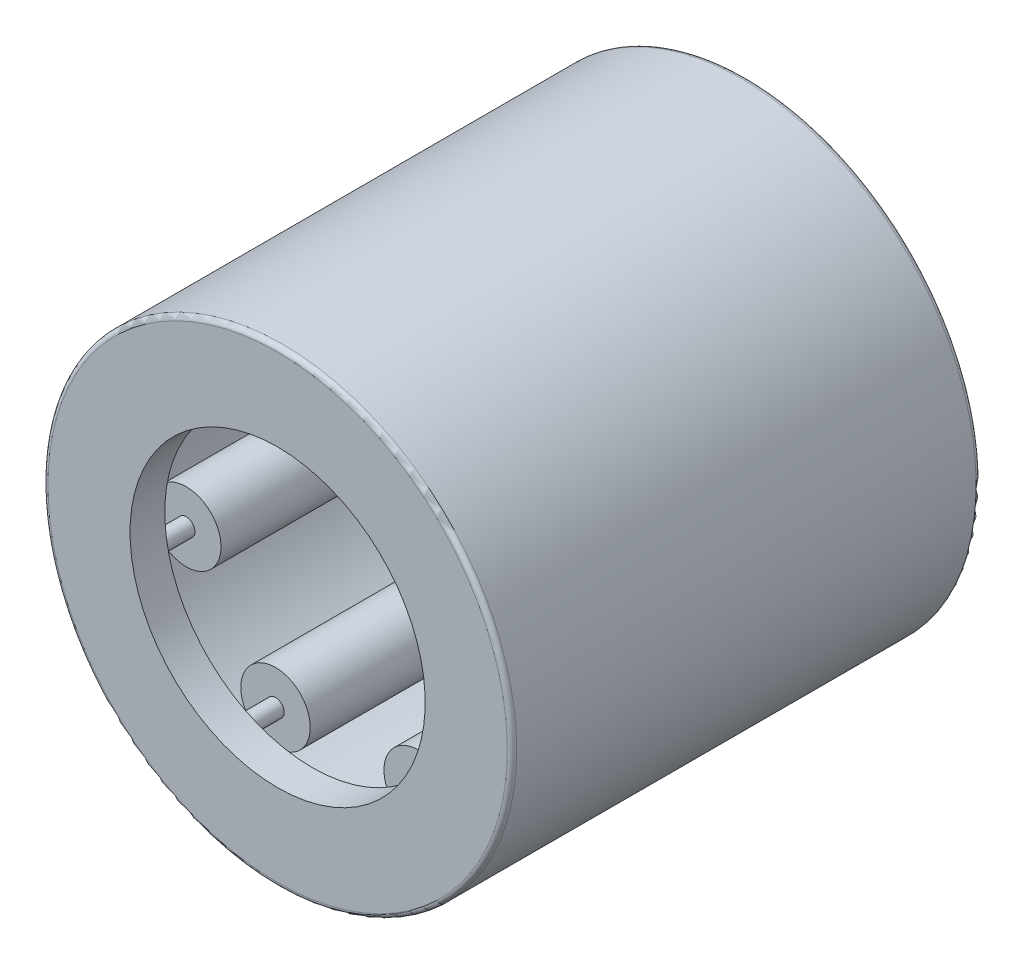
SolidWorks part; units mm, degrees
ref_plane "Front Plane" through (0, 0, 0) normal (0, 0, 1) x (1, 0, 0)
ref_plane "Top Plane" through (0, 0, 0) normal (0, 1, 0) x (1, 0, 0)
ref_plane "Right Plane" through (0, 0, 0) normal (1, 0, 0) x (0, 0, -1)
sketch "Sketch1" plane through (0, 0, 0) normal (1, 0, 0) x (0, 0, -1)
  line L0 (-4.5, 0) -> (4.5, 0) construction
  line L1 (0, 0) -> (0, 4.5) construction
  line L2 (-4.5, 0) -> (-4.5, 4.5) construction
  line L3 (-4.5, 4.5) -> (4.5, 4.5)
  line L4 (4.5, 4.5) -> (4.5, 0) construction
  line L5 (4.5, 0) -> (3.8333, 0) construction
  line L6 (3.8333, 0) -> (3.8333, 3.8333) construction
  line L7 (3.8333, 3.8333) -> (-3.8333, 3.8333)
  line L8 (-3.8333, 3.8333) -> (-3.8333, 0) construction
  line L9 (-3.8333, 0) -> (-4.5, 0) construction
  line L10 (-4.5, 4.5) -> (-4.5, 2.8333)
  line L11 (-4.5, 2.8333) -> (-3.8333, 2.8333)
  line L12 (-3.8333, 2.8333) -> (-3.8333, 3.8333)
  line L13 (3.8333, 4.5) -> (3.8333, 3.8333) construction
  line L14 (3.8333, 3.8333) -> (3.8333, 2.8333)
  line L15 (3.8333, 2.8333) -> (4.5, 2.8333)
  line L16 (4.5, 2.8333) -> (4.5, 4.5)
  line L17 (3.8333, 3.8333) -> (3.8333, 3.1667) construction
  line L18 (3.8333, 3.1667) -> (3.8333, 2.5) construction
  line L19 (3.8333, -3.8333) -> (3.8333, -3.1667) construction
  line L20 (3.8333, -4.5) -> (3.8333, -3.8333) construction
  line L21 (4.5, -2.8333) -> (4.5, -4.5) construction
  line L22 (3.8333, -2.8333) -> (4.5, -2.8333) construction
  line L23 (3.8333, -3.8333) -> (3.8333, -2.8333) construction
  line L24 (-3.8333, -2.8333) -> (-3.8333, -3.8333) construction
  line L25 (-4.5, -2.8333) -> (-3.8333, -2.8333) construction
  line L26 (-4.5, -4.5) -> (-4.5, -2.8333) construction
  line L27 (3.8333, -3.8333) -> (-3.8333, -3.8333) construction
  line L28 (-4.5, -4.5) -> (4.5, -4.5) construction
  point P4 (0, 2.5)
  dimension "C | Width" = 9
  dimension "Fw | ID" = 5
  dimension "D | OD" = 9
sketch "Sketch7" plane through (0, 0, 0) normal (1, 0, 0) x (0, 0, -1)
  line L0 (-4.5, 4.5) -> (-4.5, 2.8333) construction
  line L1 (-4.5, 2.8333) -> (-3.8333, 2.8333) construction
  line L2 (-3.8333, 2.8333) -> (-3.8333, 3.8333) construction
  line L3 (3.8333, 3.8333) -> (-3.8333, 3.8333) construction
  line L4 (3.8333, 3.8333) -> (3.8333, 2.8333) construction
  line L5 (3.8333, 2.8333) -> (4.5, 2.8333) construction
  line L6 (4.5, 2.8333) -> (4.5, 4.5) construction
  line L8 (-4.5, 4.5) -> (4.5, 4.5) construction
  line L9 (-4.5, 4.5) -> (-4.5, 2.8333)
  line L10 (-4.5, 2.8333) -> (-3.8333, 2.8333)
  line L13 (-3.8333, 2.8333) -> (-3.8333, 3.8333)
  line L16 (3.8333, 3.8333) -> (-3.8333, 3.8333)
  line L17 (3.8333, 3.8333) -> (3.8333, 2.8333)
  line L18 (3.8333, 2.8333) -> (4.5, 2.8333)
  line L19 (4.5, 2.8333) -> (4.5, 4.5)
  line L20 (-4.5, 4.5) -> (4.5, 4.5)
revolve "Revolve1" add sketch "Sketch7" angle 360 about L0
sketch "Sketch2" plane through (0, 0, 0) normal (1, 0, 0) x (0, 0, -1)
  line L0 (-4.5, 2.8333) -> (-3.8333, 2.8333) construction
  line L1 (-3.1667, 3.1667) -> (3.1667, 3.1667) construction
  line L2 (-3.1667, 3.1667) -> (-3.1667, 3.8333) construction
  line L3 (-3.1667, 3.8333) -> (3.1667, 3.8333)
  line L4 (3.1667, 3.1667) -> (3.1667, 3.8333) construction
  line L5 (3.8333, 2.8333) -> (4.5, 2.8333) construction
  line L6 (-3.8333, 3.1667) -> (-3.1667, 3.1667) construction
  line L7 (3.1667, 3.1667) -> (3.8333, 3.1667) construction
  line L8 (4.5, 4.5) -> (4.5, 0) construction
  line L9 (-3.1667, 3.3333) -> (-3.1667, 3) construction
  line L10 (-3.8333, 3.1667) -> (-3.8333, 2.8333) construction
  line L11 (-3.1667, 3.8333) -> (-3.1667, 3.3333)
  line L12 (3.1667, 3.8333) -> (3.1667, 3.3333)
  line L13 (3.1667, 3.3333) -> (-3.1667, 3.3333)
  line L14 (0, 3.8333) -> (0, 2.5) construction
  line L16 (-3.1667, 3) -> (-3.8333, 3) construction
  line L17 (0, 0) -> (4.5, 0) construction
  line L18 (-3.1667, -3) -> (-3.8333, -3) construction
  line L19 (0, -3.8333) -> (0, -2.5) construction
  line L20 (-3.8333, -3.1667) -> (-3.8333, -2.8333) construction
  line L21 (-3.1667, -3.3333) -> (-3.1667, -3) construction
  line L22 (3.1667, -3.1667) -> (3.8333, -3.1667) construction
  line L23 (-3.8333, -3.1667) -> (-3.1667, -3.1667) construction
  line L24 (3.1667, -3.1667) -> (3.1667, -3.8333) construction
  line L25 (-3.1667, -3.1667) -> (-3.1667, -3.8333) construction
  line L26 (-3.1667, -3.1667) -> (3.1667, -3.1667) construction
  line L27 (3.1667, -3.3333) -> (-3.1667, -3.3333) construction
  line L28 (3.1667, -3.8333) -> (3.1667, -3.3333) construction
  line L29 (-3.1667, -3.8333) -> (-3.1667, -3.3333) construction
  line L30 (-3.1667, -3.8333) -> (3.1667, -3.8333) construction
  line L33 (3.8333, 3.8333) -> (-3.8333, 3.8333) construction
  line L34 (3.8333, 3.8333) -> (3.8333, 2.8333) construction
  line L35 (-3.8333, 2.8333) -> (-3.8333, 3.8333) construction
  line L36 (0, 0) -> (0, 4.5) construction
  point P16 (0, 3.1667)
revolve "Revolve2" add sketch "Sketch2" angle 360 about L1
sketch "Sketch3" plane through (0, 0, 0) normal (1, 0, 0) x (0, 0, -1)
  line L1 (-3.8333, 3.1667) -> (3.8333, 3.1667)
  line L2 (-3.8333, 3.1667) -> (-3.8333, 3.3333)
  line L3 (-3.8333, 3.3333) -> (3.8333, 3.3333)
  line L4 (3.8333, 3.1667) -> (3.8333, 3.3333)
  line L5 (0, 0) -> (4.5, 0) construction
  line L7 (3.8333, -3.1667) -> (3.8333, -3.3333) construction
  line L8 (-3.8333, -3.3333) -> (3.8333, -3.3333) construction
  line L9 (-3.8333, -3.1667) -> (-3.8333, -3.3333) construction
  line L10 (-3.8333, -3.1667) -> (3.8333, -3.1667) construction
  line L11 (3.8333, 3.8333) -> (3.8333, 2.8333) construction
  line L12 (4.5, 4.5) -> (4.5, 0) construction
revolve "Revolve3" add sketch "Sketch3" angle 360 about L1
ref_axis "Axis1" through (0, 2.8333, 4.5) along (0, 1, 0)
pattern_circular "CirPattern1" count 7 every 51.429 about axis through (0, 0, 4.5) along (0, 0, -1) of bodies 166 167
fillet "Fillet1" radius 0.09 2 edges at (0, -4.5, -4.5) (0, -4.5, 4.5)
sketch "Front View" plane through (0, 0, 0) normal (0, 0, 1) x (1, 0, 0)
  circle A0 centre (0, 0) radius 2.5 construction
  circle A1 centre (0, 0) radius 4.5 construction
  dimension "ID" = 5
  dimension "OD" = 9
sketch "Right View" plane through (0, 0, 0) normal (1, 0, 0) x (0, 0, -1)
  line L0 (-4.5, 4.5) -> (4.5, 4.5) construction
  line L1 (-4.5, 4.5) -> (4.5, 4.5) construction
  line L2 (0, 0) -> (0, 4.5) construction
  point P4 (0, 4.5)
  dimension "Width" = 9
equation "\"Rollers@CirPattern1\"  = \"OD@Sketch1\"*.75"
equation "\"D1@Fillet1\" = \"D | OD@Sketch1\" * .01"
equation "\"Angle@CirPattern1\"=360 / \"Rollers@CirPattern1\""
equation "\"ID@Front View\" = \"Fw | ID@Sketch1\""
equation "\"OD@Front View\" = \"D | OD@Sketch1\""
equation "\"Width@Right View\" = \"C | Width@Sketch1\""
